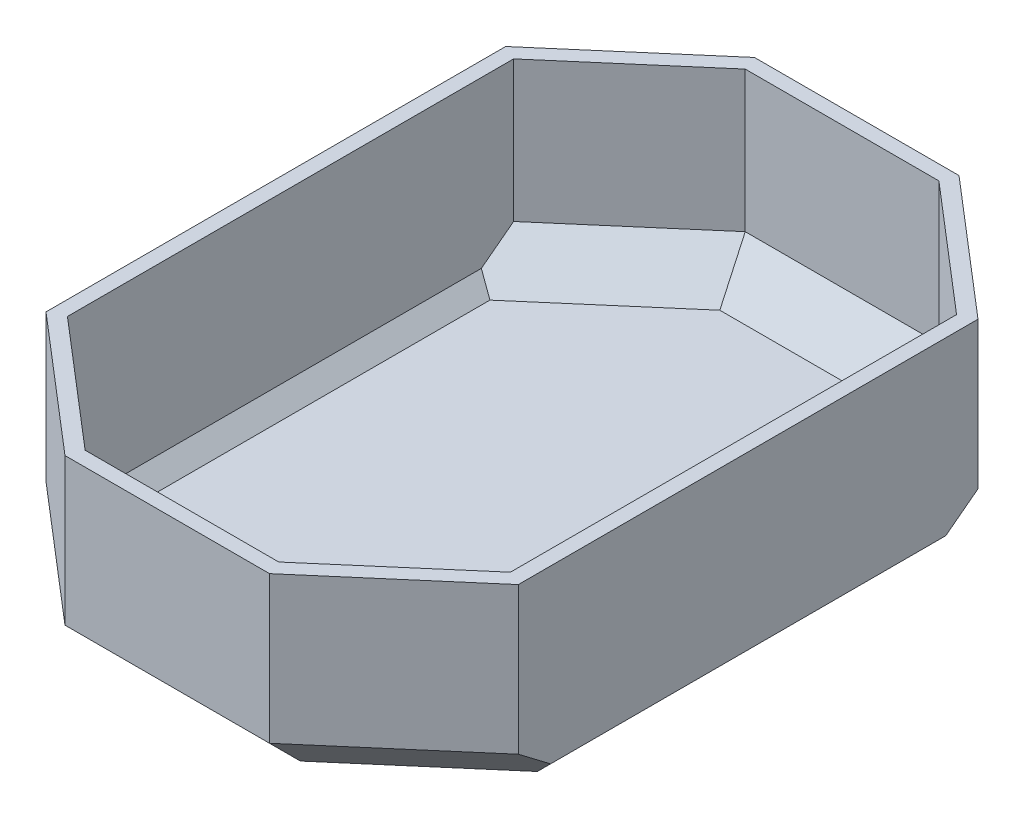
SolidWorks part; units mm, degrees
ref_plane "Front Plane" through (0, 0, 0) normal (0, 0, 1) x (1, 0, 0)
ref_plane "Top Plane" through (0, 0, 0) normal (0, 1, 0) x (1, 0, 0)
ref_plane "Right Plane" through (0, 0, 0) normal (1, 0, 0) x (0, 0, -1)
ref_axis "X" through (-88.99, 0, 0) along (1, 0, 0)
ref_axis "Y" through (0, 55, 0) along (0, -1, 0)
ref_axis "Z" through (0, 0, -88.99) along (0, 0, 1)
sketch "Sketch1" plane through (0, 0, 0) normal (0, 1, 0) x (1, 0, 0)
  line L0 (-48.2247, 46.933) -> (-20.883, 70.3995)
  line L1 (-48.2247, 46.933) -> (48.2247, 46.933)
  line L2 (-48.2247, 46.933) -> (-48.2247, -46.933)
  line L3 (-48.2247, -46.933) -> (48.2247, -46.933)
  line L4 (48.2247, 46.933) -> (48.2247, -46.933)
  line L5 (-48.2247, 46.933) -> (48.2247, -46.933) construction
  line L6 (-48.2247, -46.933) -> (48.2247, 46.933) construction
  line L7 (-20.883, 70.3995) -> (20.883, 70.3995)
  line L8 (20.883, 70.3995) -> (48.2247, 46.933)
  line L9 (0, 70.3995) -> (0, 46.933) construction
  line L10 (-48.2247, 0) -> (0, 0) construction
  line L11 (20.883, -70.3995) -> (48.2247, -46.933)
  line L12 (-20.883, -70.3995) -> (20.883, -70.3995)
  line L13 (-48.2247, -46.933) -> (-20.883, -70.3995)
  point P0 (0, 0)
extrude "Boss-Extrude1" add sketch "Sketch1" along normal blind 40 contours L4 L1 L2 L3 | L8 L7 L0 L1 | L3 L13 L12 L11 region at (0, 0, -57.1189) region at (0, 0, 0) region at (0, 0, 57.1189)
chamfer "Chamfer1" distance 10 angle 45 6 edges at (34.5539, 0, -58.6663) (0, 0, -70.3995) (-34.5539, 0, -58.6663) (-34.5539, 0, 58.6663) (0, 0, 70.3995) (34.5539, 0, 58.6663)
chamfer "Chamfer2" distance 5 angle 45 2 edges at (-48.2247, 0, 0) (48.2247, 0, 0)
shell "Shell1" thickness 3 removed face at (0, 40, 0)
